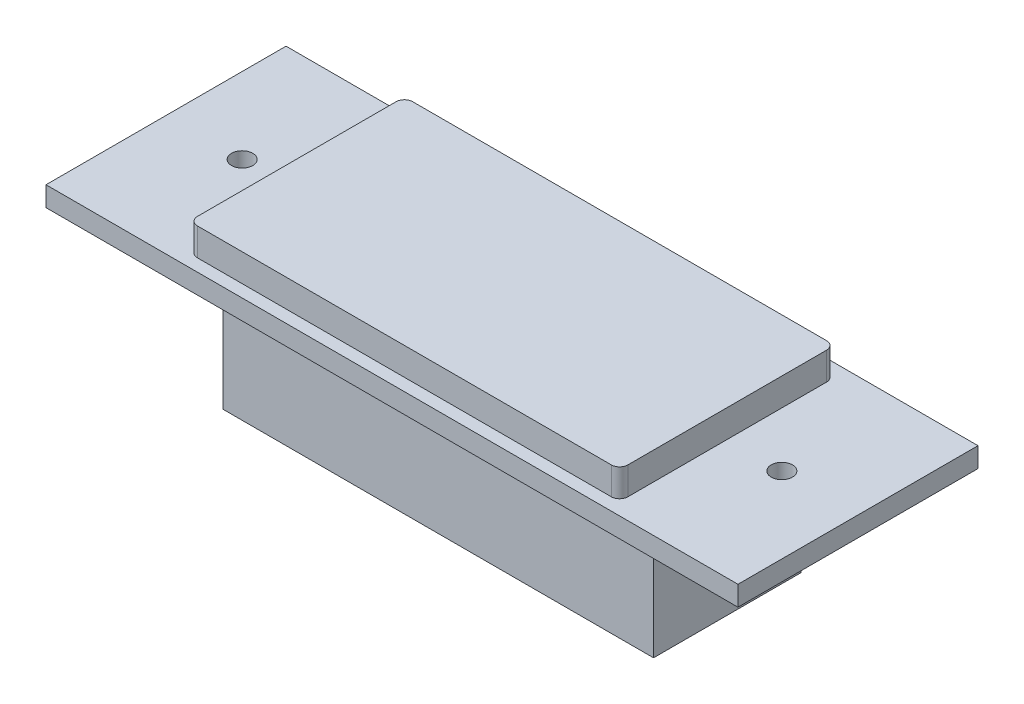
SolidWorks part; units mm, degrees
ref_plane "Front Plane" through (0, 0, 0) normal (0, 0, 1) x (1, 0, 0)
ref_plane "Top Plane" through (0, 0, 0) normal (0, 1, 0) x (1, 0, 0)
ref_plane "Right Plane" through (0, 0, 0) normal (1, 0, 0) x (0, 0, -1)
sketch "Sketch1" plane through (0, 0, 0) normal (0, 1, 0) x (1, 0, 0)
  line L1 (-33.02, 16.51) -> (33.02, 16.51)
  line L2 (-33.02, 16.51) -> (-33.02, -16.51)
  line L3 (-33.02, -16.51) -> (33.02, -16.51)
  line L4 (33.02, 16.51) -> (33.02, -16.51)
  line L5 (-33.02, 16.51) -> (33.02, -16.51) construction
  line L6 (-33.02, -16.51) -> (33.02, 16.51) construction
  point P0 (0, 0)
  dimension "D1" = 66.04
  dimension "D2" = 33.02
extrude "Boss-Extrude1" add sketch "Sketch1" along normal blind 4.2418
fillet "Fillet1" radius 1.27 4 edges at (33.02, 2.1209, 16.51) (33.02, 2.1209, -16.51) (-33.02, 2.1209, -16.51) (-33.02, 2.1209, 16.51)
sketch "Sketch2" plane through (0, 0, 0) normal (0, -1, 0) x (1, 0, 0)
  line L1 (53.086, 18.415) -> (-53.086, 18.415)
  line L2 (53.086, 18.415) -> (53.086, -18.415)
  line L3 (53.086, -18.415) -> (-53.086, -18.415)
  line L4 (-53.086, 18.415) -> (-53.086, -18.415)
  line L5 (53.086, 18.415) -> (-53.086, -18.415) construction
  line L6 (53.086, -18.415) -> (-53.086, 18.415) construction
  point P0 (0, 0)
  dimension "D1" = 36.83
  dimension "D2" = 106.172
extrude "Boss-Extrude2" add sketch "Sketch2" along normal blind 3.048
sketch "Sketch3" plane through (0, 0, 0) normal (0, 1, 0) x (1, 0, 0)
  line L0 (-53.086, 0) -> (-41.402, 0) construction
  line L1 (-53.086, -18.415) -> (-53.086, 18.415) construction
  line L2 (-41.402, 0) -> (41.402, 0) construction
  line L3 (41.402, 0) -> (53.086, 0) construction
  line L4 (53.086, 18.415) -> (53.086, -18.415) construction
  dimension "D1" = 82.804
hole_wizard "#4 Clearance Hole1" positions "Sketch4" profile "Sketch5" hole size "#4" standard "ANSI Inch" end condition through all
sketch "Sketch4" plane through (0, 0, 0) normal (0, 1, 0) x (1, 0, 0)
  point P0 (-41.402, 0)
  point P3 (41.402, 0)
sketch "Sketch5" plane through (-41.402, 0, 0) normal (1, 0, 0) x (0, 0, 1)
  line L0 (0, 0) -> (0, 3.048)
  line L1 (0, 3.048) -> (1.6319, 3.048)
  line L2 (1.6319, 3.048) -> (1.6319, 0)
  line L5 (1.6319, 0) -> (0, 0)
  line L11 (0, -6.35) -> (0, 107.95) construction
  dimension "Thru Hole Dia." = 3.2639
  dimension "Thru Hole Depth" = 3.048
sketch "Sketch6" plane through (0, -3.048, 0) normal (0, -1, 0) x (1, 0, 0)
  line L1 (33.02, 11.303) -> (-33.02, 11.303)
  line L2 (33.02, 11.303) -> (33.02, -11.303)
  line L3 (33.02, -11.303) -> (-33.02, -11.303)
  line L4 (-33.02, 11.303) -> (-33.02, -11.303)
  line L5 (33.02, 11.303) -> (-33.02, -11.303) construction
  line L6 (33.02, -11.303) -> (-33.02, 11.303) construction
  point P0 (0, 0)
  dimension "D1" = 66.04
  dimension "D2" = 22.606
extrude "Boss-Extrude3" add sketch "Sketch6" along normal blind 20.32
